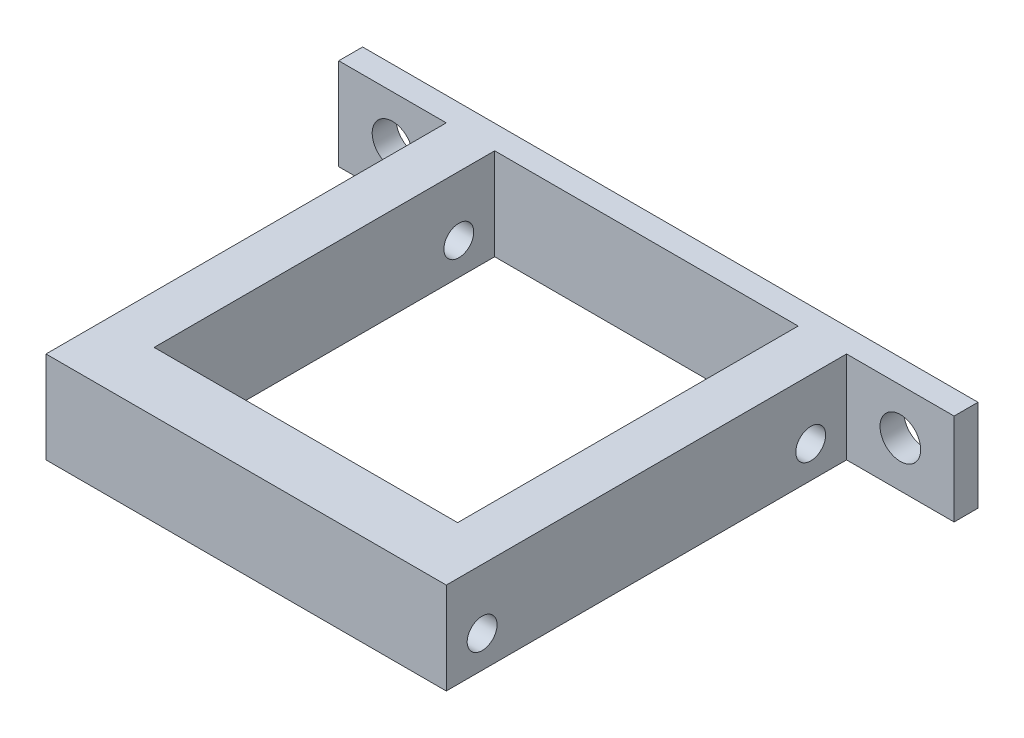
SolidWorks part; units mm, degrees
ref_plane "Front Plane" through (0, 0, 0) normal (0, 0, 1) x (1, 0, 0)
ref_plane "Top Plane" through (0, 0, 0) normal (0, 1, 0) x (1, 0, 0)
ref_plane "Right Plane" through (0, 0, 0) normal (1, 0, 0) x (0, 0, -1)
sketch "Sketch25" plane through (0, 0, 0) normal (0, 1, 0) x (1, 0, 0)
  line L1 (25.75, 28.75) -> (-25.75, 28.75)
  line L2 (25.75, 28.75) -> (25.75, 26.75)
  line L3 (25.75, 26.75) -> (16.75, 26.75)
  line L4 (-25.75, 28.75) -> (-25.75, 26.75)
  line L5 (16.75, -6.75) -> (-16.75, -6.75)
  line L6 (16.75, 26.75) -> (16.75, -6.75)
  line L8 (12.7, 26.75) -> (12.7, -1.75)
  line L9 (-16.75, 26.75) -> (-25.75, 26.75)
  line L10 (12.7, 26.75) -> (-12.7, 26.75)
  line L11 (-16.75, 26.75) -> (-16.75, -6.75)
  line L13 (-12.7, 26.75) -> (-12.7, -1.75)
  line L16 (-12.7, -1.75) -> (12.7, -1.75)
  point P7 (0, -6.75)
  point P14 (0, -1.75)
  dimension "D1" = 9
  dimension "D2" = 9
  dimension "D3" = 25.4
  dimension "D4" = 33.5
  dimension "D5" = 51.5
  dimension "D6" = 2
  dimension "D7" = 5
extrude "Boss-Extrude5" add sketch "Sketch25" against normal blind 7.68 separate body
hole_wizard "M3x0.5 Tapped Hole2" positions "3DSketch4" profile "Sketch6" tap size "M3x0.5" standard "ANSI Metric"
sketch3d "3DSketch4"
  line L4 (16.75, -7.68, 6.75) -> (16.75, -7.68, -26.75) construction
  line L5 (16.75, 0, 6.75) -> (16.75, 0, -26.75) construction
  line L9 (16.75, -7.68, -10) -> (16.75, 0, -10) construction
  line L10 (16.75, -5, -23.75) -> (16.75, -5, 3.75) construction
  line L11 (16.75, -7.68, -26.75) -> (16.75, 0, -26.75) construction
  point P13 (16.75, -5, 3.75)
  point P15 (16.75, -5, -23.75)
  point P17 (-16.75, -5, -23.75)
  point P26 (-16.75, -5, 3.75)
  point P53 (16.75, -5, -10)
  dimension "D1" = 16.75
  dimension "D2" = 27.5
  dimension "D7" = 2.68
sketch "Sketch6" plane through (16.75, -5, 3.75) normal (0, 1, 0) x (0, 0, -1)
  line L0 (0, 0) -> (0, 8.3711)
  line L1 (0, 8.3711) -> (1.25, 7.62)
  line L2 (1.25, 7.62) -> (1.25, 0)
  line L5 (1.25, 0) -> (0, 0)
  line L10 (0, 8.3711) -> (-1.25, 7.62) construction
  line L11 (0, -6.35) -> (0, 107.95) construction
  dimension "Tap Drill Dia." = 2.5
  dimension "Tap Drill Depth" = 7.62
  dimension "Drill Angle" = 118
hole_wizard "M3 Clearance Hole3" positions "3DSketch7" profile "Sketch23" hole size "M3" standard "ANSI Metric" end condition through all
sketch3d "3DSketch7"
  line L5 (16.75, 0, -26.75) -> (25.75, 0, -26.75) construction
  line L6 (25.75, -7.68, -26.75) -> (25.75, 0, -26.75) construction
  line L8 (-25.75, -7.68, -26.75) -> (-16.75, -7.68, -26.75) construction
  point P0 (21.25, -3.84, -26.75)
  point P2 (-21.25, -3.84, -26.75)
  point P27 (21.25, 0, -26.75)
  point P31 (25.75, -3.84, -26.75)
  point P38 (-21.25, -7.68, -26.75)
sketch "Sketch23" plane through (21.25, -3.84, -26.75) normal (1, 0, 0) x (0, -1, 0)
  line L0 (0, 0) -> (0, 2)
  line L1 (0, 2) -> (1.7, 2)
  line L2 (1.7, 2) -> (1.7, 0)
  line L5 (1.7, 0) -> (0, 0)
  line L11 (0, -6.35) -> (0, 107.95) construction
  dimension "Thru Hole Dia." = 3.4
  dimension "Thru Hole Depth" = 2
